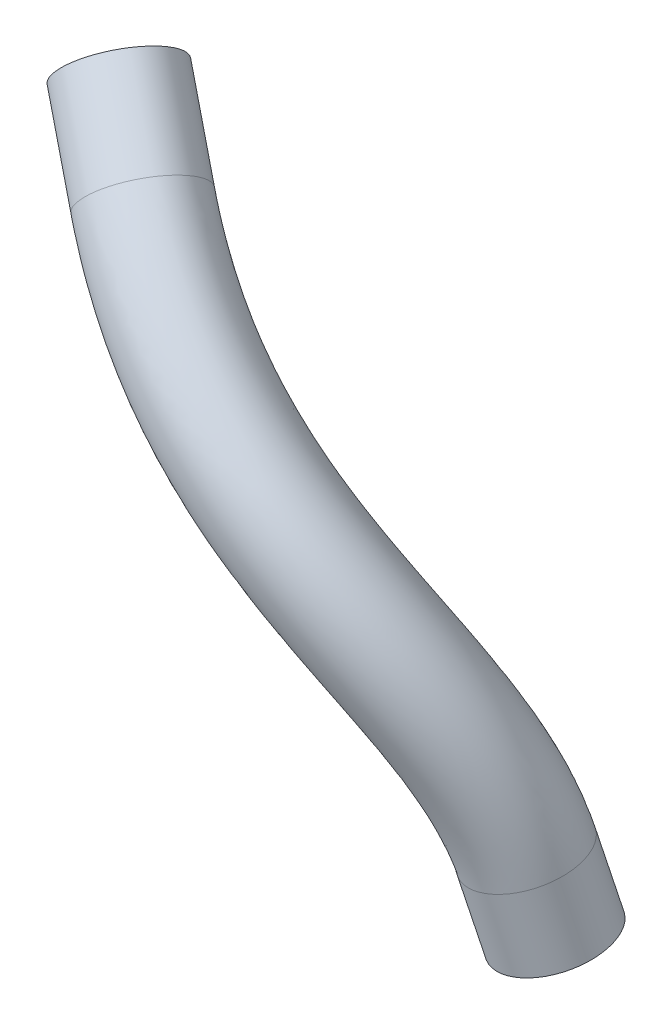
SolidWorks part; units mm, degrees
material "Silicon Rubber"
ref_plane "X-Y Datum" through (0, 0, 0) normal (0, 0, 1) x (1, 0, 0)
ref_plane "X-Z Datum" through (0, 0, 0) normal (0, 1, 0) x (1, 0, 0)
ref_plane "Y-Z Datum" through (0, 0, 0) normal (1, 0, 0) x (0, 0, -1)
sketch3d "3DSketch1"
  line L0 (27.5015, -11.1, -13.9429) -> (23.0956, 7.1738, -10.8516)
  line L1 (-71.5027, 110.3168, -5.1318) -> (-88.6777, 125.4988, -16.072)
  line L2 (-71.5027, 110.3168, -5.1318) -> (-88.6777, 125.4988, -16.072) construction
  line L3 (-88.6777, 125.4988, -16.072) -> (-76.1683, 114.441, -8.1038) construction
  line L4 (-88.6777, 125.4988, -16.072) -> (-10.2107, 56.1369, 33.9101) construction
  line L5 (23.0956, 7.1738, -10.8516) -> (24.827, -0.0072, -12.0664) construction
  circle A0 centre (-76.1683, 114.441, -8.1038) radius 9.5 construction
  circle A1 centre (-88.6777, 125.4988, -16.072) radius 9.5 construction
  circle A4 centre (-76.1683, 114.441, -8.1038) radius 9.5 construction
  circle A5 centre (-88.6777, 125.4988, -16.072) radius 9.5 construction
  circle A14 centre (23.0956, 7.1738, -10.8516) radius 9.525 construction
  circle A15 centre (24.827, -0.0072, -12.0664) radius 9.9344 construction
  circle A16 centre (23.0956, 7.1738, -10.8516) radius 9.525 construction
  circle A17 centre (24.827, -0.0072, -12.0664) radius 9.9344 construction
  spline S0 degree 3 poles (23.0956, 7.1738, -10.8516) (13.2611, 47.9635, -3.9512) (-24.9952, 69.2059, 24.4926) (-71.5027, 110.3168, -5.1318) knots 0 0 0 0 1 1 1 1
  point P8 (-82.5921, 120.1193, -12.1956)
  point P11 (-95.1014, 131.1771, -20.1638)
  point P13 (-82.5921, 120.1193, -12.1956)
  point P15 (20.8927, 16.3108, -9.3059)
  point P19 (22.5294, 9.5224, -10.4543)
  point P21 (20.8927, 16.3108, -9.3059)
  point P24 (22.5294, 9.5224, -10.4543)
  point P26 (-95.1014, 131.1771, -20.1638)
  dimension "D2" = 19.05
  dimension "D1" = 25.4
sweep "Sweep1" add path "3DSketch1" circular profile diameter 26.9875 parameters "D3"=26.9875
sweep "Cut-Sweep1" cut path "3DSketch1<2>" circular profile diameter 19.05 parameters "D3"=19.05
sketch3d "3DSketch1<2>" same geometry as "3DSketch1"
